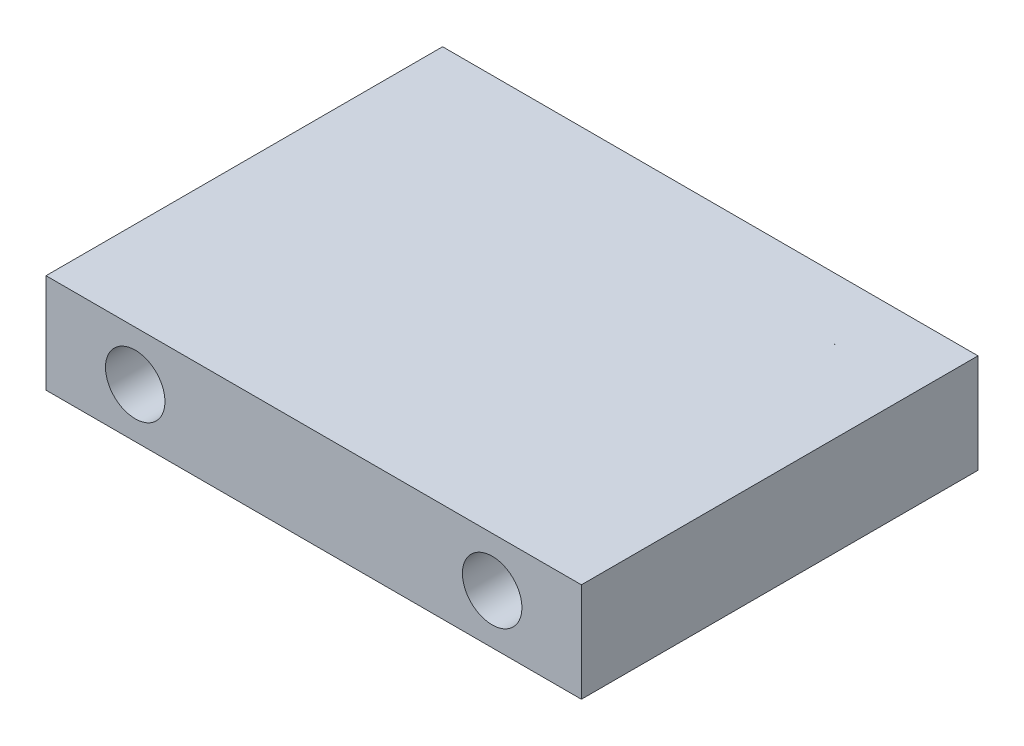
SolidWorks part; units mm, degrees
ref_plane "Front Plane" through (0, 0, 0) normal (0, 0, 1) x (1, 0, 0)
ref_plane "Top Plane" through (0, 0, 0) normal (0, 1, 0) x (1, 0, 0)
ref_plane "Right Plane" through (0, 0, 0) normal (1, 0, 0) x (0, 0, -1)
sketch "Sketch1" plane through (0, 0, 0) normal (0, 1, 0) x (1, 0, 0)
  line L1 (0, 0) -> (27, 0)
  line L2 (0, 0) -> (0, 20)
  line L3 (0, 20) -> (27, 20)
  line L4 (27, 0) -> (27, 20)
  dimension "D1" = 27
  dimension "D2" = 20
extrude "Boss-Extrude1" add sketch "Sketch1" along normal blind 5
sketch "Sketch2" plane through (0, 0, 0) normal (0, 0, 1) x (1, 0, 0)
  line L0 (0, 5) -> (0, 0) construction
  line L1 (0, 5) -> (27, 5) construction
  line L3 (27, 5) -> (27, 0) construction
  circle A0 centre (4.5, 2.5) radius 1.5
  circle A1 centre (22.5, 2.5) radius 1.5
  dimension "D1" = 4.5
  dimension "D2" = 2.5
  dimension "D3" = 2.5
  dimension "D4" = 4.5
extrude "Cut-Extrude1" cut sketch "Sketch2" against normal blind 1000 and the other way blind 1000
